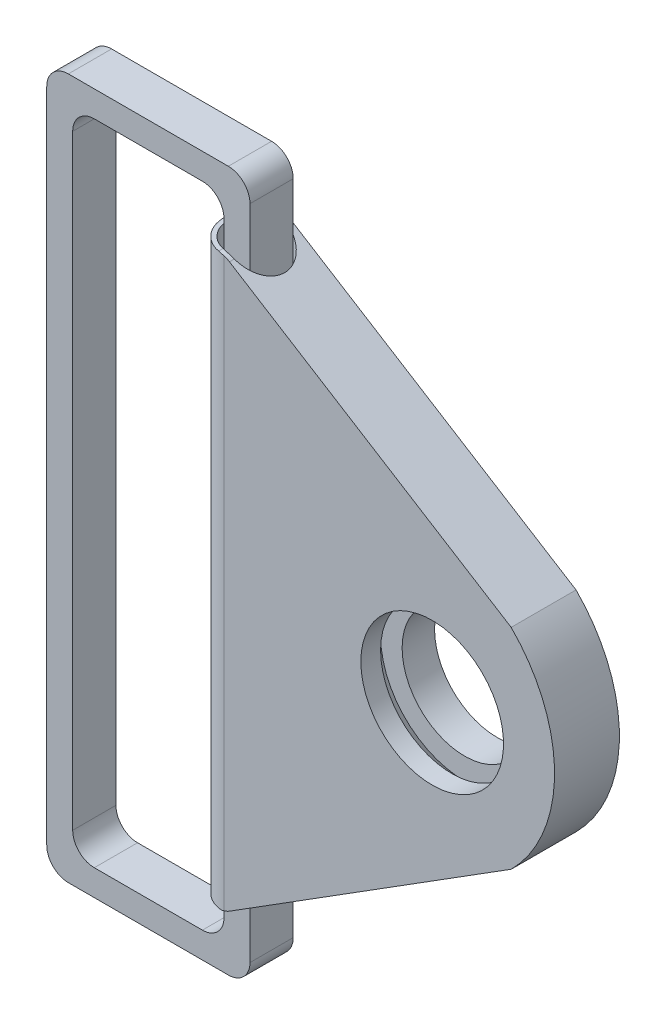
SolidWorks part; units mm, degrees
ref_plane "Piano frontale" through (0, 0, 0) normal (0, 0, 1) x (1, 0, 0)
ref_plane "Piano superiore" through (0, 0, 0) normal (0, 1, 0) x (1, 0, 0)
ref_plane "Piano destro" through (0, 0, 0) normal (1, 0, 0) x (0, 0, -1)
sketch "Schizzo1" plane through (0, 0, 0) normal (0, 0, 1) x (1, 0, 0)
  line L0 (0, 13.0495) -> (0, -13.2681)
  line L1 (0, -13.2681) -> (13.2739, -4.9218)
  line L2 (0, 13.0495) -> (13.2739, 4.7706)
  arc A0 (13.2739, -4.9218) -> (13.2739, 4.7706) centre (8.4277, -0.0756) ccw
  circle A1 centre (9.6206, -0.0756) radius 2.89
extrude "Estrusione-Estrusione1" add sketch "Schizzo1" along normal mid plane 3
sketch "Schizzo2" plane through (0, 0, 0) normal (0, 1, 0) x (1, 0, 0)
  circle A0 centre (0, 0) radius 1.5
extrude "Estrusione-Estrusione3" add sketch "Schizzo2" against normal up to surface and the other way up to surface up to face at (6.6369, -9.095, 0) other way up to face at (6.6369, 8.9101, 0)
sketch "Schizzo4" plane through (0, 0, 0) normal (0, 1, 0) x (1, 0, 0)
  circle A0 centre (0, 0) radius 1.2978
extrude "Taglio-Estrusione2" cut sketch "Schizzo4" against normal up to surface and the other way up to surface up to face at (6.2619, -9.3308, 0) other way up to face at (6.2619, 9.144, 0)
sketch "Schizzo5" plane through (0, 0, 0) normal (0, 0, 1) x (1, 0, 0)
  line L0 (0, 13.0495) -> (-1.5, 13.0495)
  line L1 (-1.5, 13.9851) -> (-1.5, -14.2113) construction
  line L2 (-1.5, 13.0495) -> (-1.5, 13.9851)
  line L3 (-1.5, 13.9851) -> (0, 13.0495)
  line L4 (0, -13.2681) -> (-1.5, -13.2681)
  line L5 (-1.5, -13.2681) -> (-1.5, -14.2113)
  line L6 (-1.5, -14.2113) -> (0, -13.2681)
extrude "Taglio-Estrusione3" cut sketch "Schizzo5" along normal through all both and the other way through all
fillet "Raccordo3" radius 1 2 edges at (0, 13.0495, -1.3989) (0, 13.0495, 1.3989)
fillet "Raccordo4" radius 1 2 edges at (0, -13.2681, -1.3989) (0, -13.2681, 1.3989)
sketch "Schizzo8" plane through (0, 0, 0) normal (0, 0, 1) x (1, 0, 0)
  line L5 (-0.5079, 15) -> (-0.5079, -15)
  line L6 (-0.5079, 15) -> (-7.5079, 15)
  line L7 (-0.5079, -15) -> (-7.5079, -15)
  line L8 (-7.5079, 15) -> (-7.5079, -15)
  dimension "D1" = 15
  dimension "D2" = 7
  dimension "D3" = 15
  dimension "D4" = 0.5079
extrude "Estrusione-Sottile1" add sketch "Schizzo8" along normal mid plane 2 separate body thin thin type one direction wall 1.2
fillet "Raccordo9" radius 1 4 edges at (0.6921, -16.2, 0) (-8.7079, -16.2, 0) (0.6921, 16.2, 0) (-8.7079, 16.2, 0) first distance on face at (-4.0079, -16.2, 0) first distance on face at (-4.0079, 16.2, 0)
fillet "Raccordo10" radius 1 4 edges at (-0.5079, -15, 0) (-7.5079, -15, 0) (-0.5079, 15, 0) (-7.5079, 15, 0) first distance on face at (-0.5079, 0, 0) first distance on face at (-7.5079, 0, 0)
hole_wizard "Foro filettato G1/16-1" positions "Schizzo9" profile "Schizzo10" tap size "G1/16" standard "GB" end condition through all
sketch "Schizzo9" plane through (0, 0, 0) normal (0, 0, 1) x (1, 0, 0)
  point P0 (9.6206, -0.0756)
sketch "Schizzo10" plane through (9.6206, -0.0756, 0) normal (1, 0, 0) x (0, 1, 0)
  line L0 (0, 0) -> (0, 1.5)
  line L1 (0, 1.5) -> (3.3, 1.5)
  line L2 (3.3, 1.5) -> (3.3, 0.5865)
  line L3 (3.3, 0.5865) -> (3.8865, 0)
  line L5 (3.8865, 0) -> (0, 0)
  line L6 (-3.3, 0.5865) -> (-3.8865, 0) construction
  line L11 (0, -6.35) -> (0, 107.95) construction
  dimension "Thru Tap Drill Dia." = 6.6
  dimension "Thru Tap Drill Depth" = 1.5
  dimension "Near C'Sink Dia." = 7.773
  dimension "Near C'Sink Angle" = 90
cosmetic thread "Filettatura del foro1" parameters "D2"=7.723
